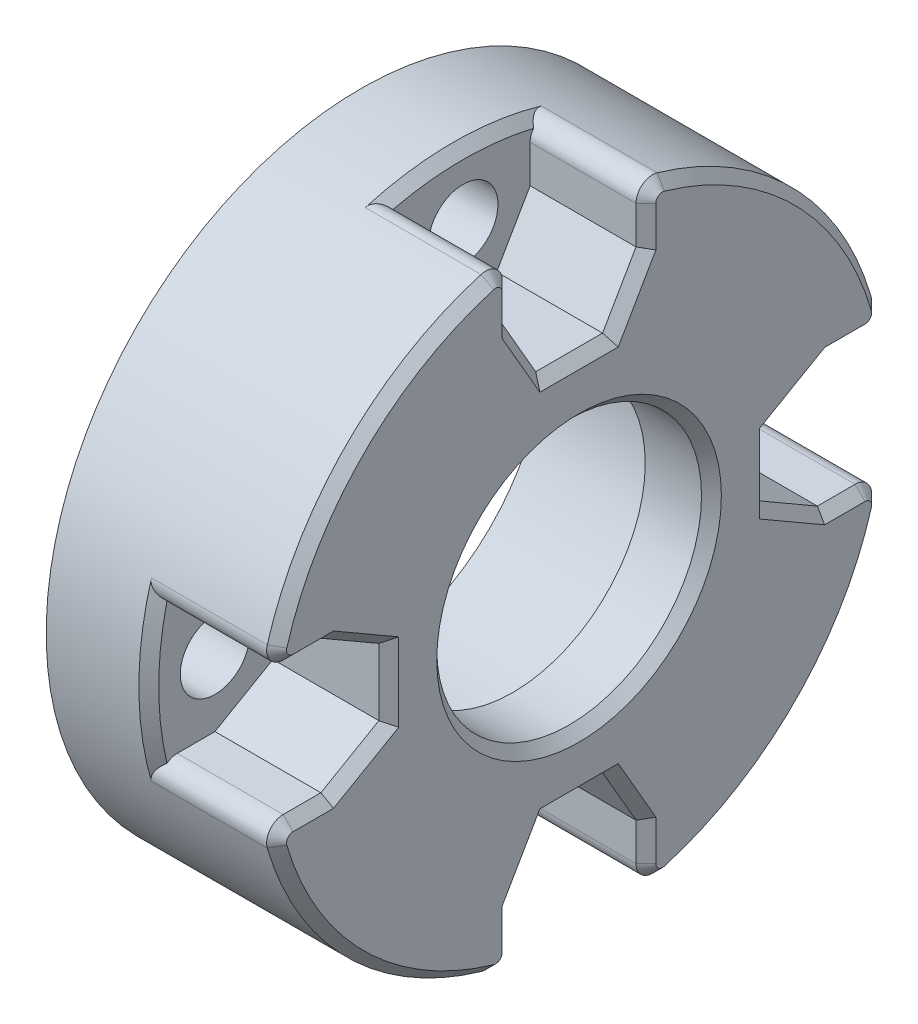
SolidWorks part; units mm, degrees
ref_plane "Front Plane" through (0, 0, 0) normal (0, 0, 1) x (1, 0, 0)
ref_plane "Top Plane" through (0, 0, 0) normal (0, 1, 0) x (1, 0, 0)
ref_plane "Right Plane" through (0, 0, 0) normal (1, 0, 0) x (0, 0, -1)
sketch "Sketch1" plane through (0, 0, 0) normal (0, 0, 1) x (1, 0, 0)
  line L0 (-9.2, 19) -> (4, 19)
  line L1 (4, 19) -> (4, 8)
  line L2 (4, 8) -> (0, 8)
  line L3 (0, 8) -> (0, 11.1)
  line L4 (0, 11.1) -> (-9.2, 11.1)
  line L5 (-9.2, 11.1) -> (-9.2, 19)
  line L6 (0, 0) -> (-14.1131, 0) construction
  dimension "D1" = 16
  dimension "D2" = 9.2
  dimension "D3" = 4
  dimension "D4" = 38
  dimension "D5" = 22.2
revolve "Revolve1" add sketch "Sketch1" angle 360 about L6
sketch "Sketch2" plane through (-9.2, 0, 0) normal (-1, 0, 0) x (0, 0, 1)
  circle A0 centre (0, 0) radius 15 construction
  circle A1 centre (-15, 0) radius 2.1
  dimension "D1" = 30
  dimension "D2" = 4.2
extrude "Cut-Extrude1" cut sketch "Sketch2" against normal through all
pattern_circular "CirPattern1" count 4 over 360 about axis through (0, 0, 0) along (1, 0, 0) of "Cut-Extrude1" reverse direction yes
chamfer "Chamfer1" distance 0.6 angle 45 1 edges at (4, 0, -19)
sketch "Sketch3" plane through (4, 0, 0) normal (1, 0, 0) x (0, 0, -1)
  line L0 (-15, 4.0415) -> (-20, 4.0415)
  line L1 (-15, 4.0415) -> (-18.5, 2.0207) construction
  line L2 (-18.5, 2.0207) -> (-18.5, -2.0207) construction
  line L3 (-18.5, -2.0207) -> (-15, -4.0415) construction
  line L4 (-15, -4.0415) -> (-11.5, -2.0207)
  line L5 (-11.5, -2.0207) -> (-11.5, 2.0207)
  line L6 (-11.5, 2.0207) -> (-15, 4.0415)
  line L7 (-20, 4.0415) -> (-20, -4.0415)
  line L8 (-20, -4.0415) -> (-15, -4.0415)
  circle A0 centre (-15, 0) radius 3.5 construction
  dimension "D1" = 7
  dimension "D2" = 5
extrude "Cut-Extrude2" cut sketch "Sketch3" against normal blind 7
pattern_circular "CirPattern2" count 4 over 360 about axis through (0, 0, 0) along (1, 0, 0) of "Cut-Extrude2"
fillet "Fillet1" radius 1 8 edges at (0.2, -4.0415, 18.5652) (0.2, -18.5652, 4.0415) (0.2, -18.5652, -4.0415) (0.2, -4.0415, -18.5652) (0.2, 4.0415, -18.5652) (0.2, 18.5652, -4.0415) (0.2, 18.5652, 4.0415) (0.2, 4.0415, 18.5652)
chamfer "Chamfer2" distance 0.6 angle 45 4 edges at (-3, -19, 0) (-3, 0, -19) (-3, 19, 0) (-3, 0, 19)
chamfer "Chamfer3" distance 0.6 angle 45 28 edges at (4, -4.0971, 17.6084) (4, 4.0971, 17.6084) (4, -4.0415, 16.1398) (4, 4.0415, 16.1398) (4, -3.0311, 13.25) (4, 3.0311, 13.25) (4, 0, 11.5) (4, -17.6084, 4.0971) (4, -17.6084, -4.0971) (4, -16.1398, 4.0415) (4, -13.25, 3.0311) (4, -11.5, 0) (4, -16.1398, -4.0415) (4, -13.25, -3.0311) (4, -4.0971, -17.6084) (4, 4.0971, -17.6084) (4, -4.0415, -16.1398) (4, -3.0311, -13.25) (4, 0, -11.5) (4, 3.0311, -13.25) (4, 4.0415, -16.1398) (4, 17.6084, 4.0971) (4, 17.6084, -4.0971) (4, 16.1398, 4.0415) (4, 13.25, 3.0311) (4, 11.5, 0) (4, 16.1398, -4.0415) (4, 13.25, -3.0311)
chamfer "Chamfer4" distance 0.6 angle 45 1 edges at (4, 0, -8)
